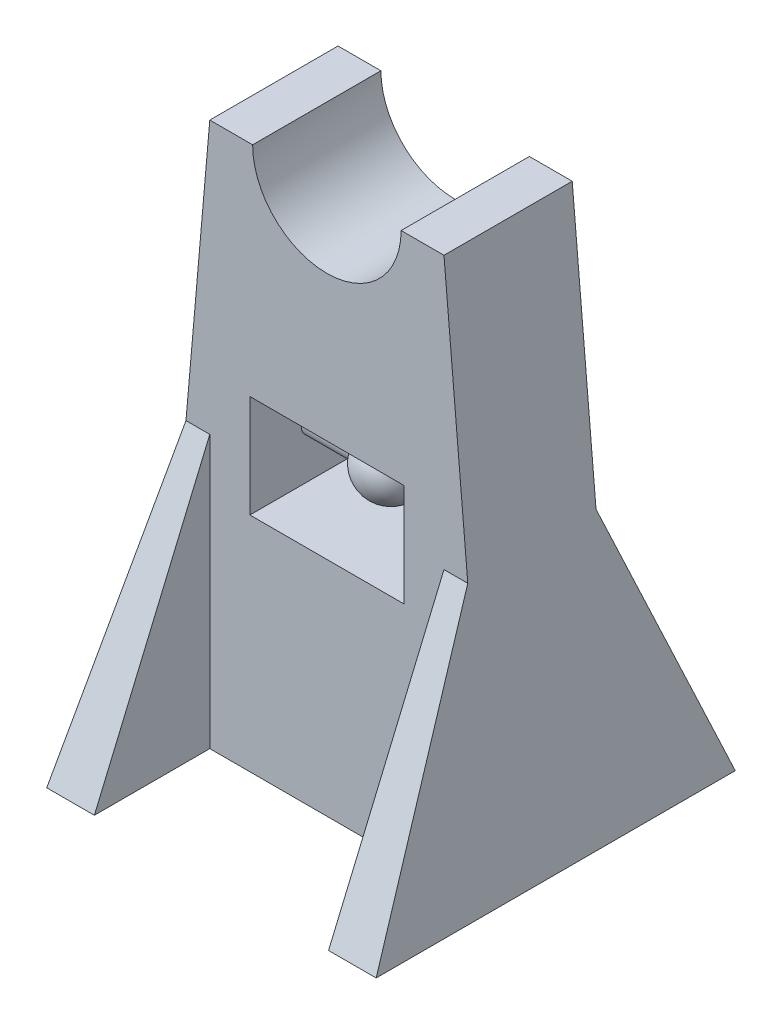
SolidWorks part; units mm, degrees
ref_plane "Front Plane" through (0, 0, 0) normal (0, 0, 1) x (1, 0, 0)
ref_plane "Top Plane" through (0, 0, 0) normal (0, 1, 0) x (1, 0, 0)
ref_plane "Right Plane" through (0, 0, 0) normal (1, 0, 0) x (0, 0, -1)
sketch "Sketch1" plane through (0, 0, 0) normal (0, 0, 1) x (1, 0, 0)
  line L0 (0, 0) -> (0, -212.2426) construction
  circle A0 centre (0, 0) radius 100 construction
  circle A1 centre (0, 0) radius 28.9435 construction
ref_plane "Plane1" through (0, -212.2426, 0) normal (0, 1, 0) x (1, 0, 0)
sketch "Sketch2" plane through (0, 0, 0) normal (0, 0, 1) x (1, 0, 0)
  line L0 (-28.9435, 0) -> (-45.6516, 0)
  line L1 (-45.6516, 0) -> (-64.2205, -212.2426)
  line L2 (77, -212.2426) -> (-77, -212.2426) construction
  line L3 (-64.2205, -212.2426) -> (64.2205, -212.2426)
  line L4 (0, -77) -> (0, 77) construction
  line L5 (45.6516, 0) -> (64.2205, -212.2426)
  line L6 (28.9435, 0) -> (45.6516, 0)
  line L7 (-45.6516, 0) -> (-45.6516, -212.2426) construction
  line L12 (-30, -85.527) -> (30, -85.527)
  line L13 (-30, -85.527) -> (-30, -125.527)
  line L14 (-30, -125.527) -> (30, -125.527)
  line L15 (30, -85.527) -> (30, -125.527)
  line L16 (45.6516, 0) -> (45.6516, -212.2426) construction
  line L17 (-45.6516, -106.1213) -> (-54.936, -106.1213) construction
  line L18 (45.6516, -106.1213) -> (54.936, -106.1213) construction
  arc A0 (-28.9435, 0) -> (28.9435, 0) centre (0, 0) ccw
  circle A1 centre (0, 0) radius 28.9435 construction
  point P16 (0, -212.2426)
  point P26 (0, 0)
  point P27 (0, 0)
  dimension "D1" = 40
  dimension "D2" = 16.7081
  dimension "D3" = 60
extrude "Boss-Extrude1" add sketch "Sketch2" along normal blind 25 and the other way blind 25
ref_plane "Plane2" through (-45.6516, 0, 0) normal (1, 0, 0) x (0, 0, -1)
sketch "Sketch57" plane through (0, 0, -25) normal (0, 0, -1) x (-1, 0, 0)
  line L0 (-45.6516, 0) -> (-45.6516, -212.2426) construction
  line L2 (-54.936, -106.1213) -> (-45.6516, -106.1213) construction
  line L4 (45.6516, -106.1213) -> (54.936, -106.1213)
  line L6 (64.2205, -212.2426) -> (-64.2205, -212.2426) construction
  line L7 (45.6516, -212.2426) -> (45.6516, 0) construction
sketch "Sketch58" plane through (-45.6516, 0, 0) normal (1, 0, 0) x (0, 0, -1)
  line L0 (25, -212.2426) -> (25, 0) construction
  line L1 (25, -106.1213) -> (25, -212.2426)
  line L2 (25, -212.2426) -> (70, -212.2426)
  line L3 (27.5, -212.2426) -> (-27.5, -212.2426) construction
  line L4 (70, -212.2426) -> (25, -106.1213)
  line L5 (0, 110) -> (0, -110) construction
  line L6 (-25, -212.2426) -> (-70, -212.2426)
  line L7 (-25, -106.1213) -> (-25, -212.2426)
  line L8 (-70, -212.2426) -> (-25, -106.1213)
  dimension "D1" = 45
extrude "Boss-Extrude7" add sketch "Sketch58" against normal up to surface (109.8721 mm away) up to face at (-54.936, -106.1213, 0)
ref_plane "Plane6" through (45.6516, 0, 0) normal (1, 0, 0) x (0, 0, -1)
sketch "Sketch59" plane through (45.6516, 0, 0) normal (1, 0, 0) x (0, 0, -1)
  line L0 (25, -106.1213) -> (25, -212.2426)
  line L1 (25, -212.2426) -> (25, 0) construction
  line L2 (25, 0) -> (25, -212.2426) construction
  line L3 (77, -212.2426) -> (-77, -212.2426) construction
  line L4 (25, -212.2426) -> (70, -212.2426)
  line L5 (70, -212.2426) -> (25, -106.1213)
  line L6 (0, 110) -> (0, -110) construction
  line L7 (-25, -212.2426) -> (-70, -212.2426)
  line L8 (-25, -106.1213) -> (-25, -212.2426)
  line L9 (-70, -212.2426) -> (-25, -106.1213)
  dimension "D1" = 45
extrude "Boss-Extrude8" add sketch "Sketch59" along normal up to surface (18.5688 mm away) up to face at (54.936, -106.1213, 0)
sketch "Sketch60" plane through (0, 0, 0) normal (0, 0, 1) x (1, 0, 0)
  line L3 (0, 0) -> (0, -212.2426) construction
  line L4 (0, -93.527) -> (0, -117.527)
  arc A0 (0, -93.527) -> (0, -117.527) centre (0, -105.527) ccw
revolve "Revolve9" add sketch "Sketch60" angle 360 about L0 region at (-5.093, -105.527, 0)
sketch "Sketch62" plane through (0, 0, 0) normal (0, 0, 1) x (1, 0, 0)
  line L0 (30, -105.527) -> (-30, -105.527)
  line L1 (30, -85.527) -> (30, -125.527) construction
  line L2 (-30, -85.527) -> (-30, -125.527) construction
sweep "Sweep3" add path "Sketch62" circular profile diameter 10 parameters "D3"=10
